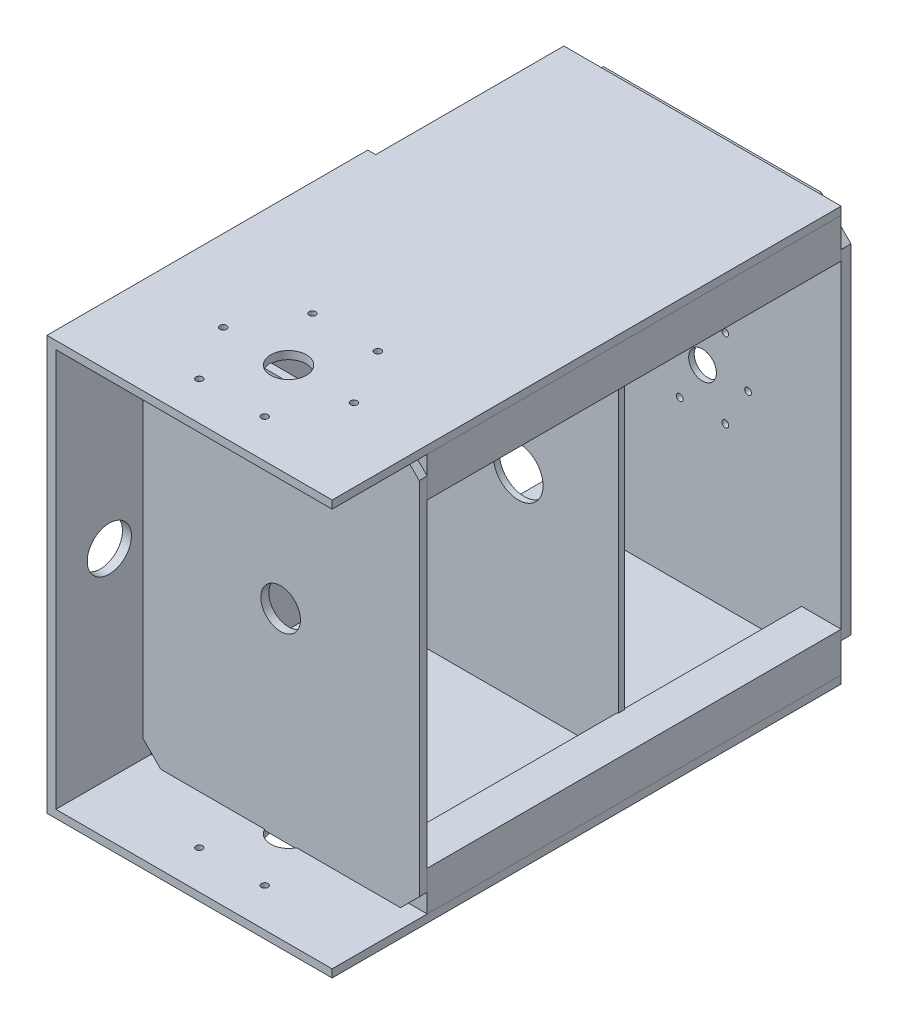
SolidWorks part; units mm, degrees
ref_plane "Front Plane" through (0, 0, 0) normal (0, 0, 1) x (1, 0, 0)
ref_plane "Top Plane" through (0, 0, 0) normal (0, 1, 0) x (1, 0, 0)
ref_plane "Right Plane" through (0, 0, 0) normal (1, 0, 0) x (0, 0, -1)
sketch "SK_Bottom_Plate" plane through (0, 0, 0) normal (0, 0, 1) x (1, 0, 0)
  line L0 (-55, -100.5) -> (55, -100.5)
  line L1 (55, -100.5) -> (70, -85.5)
  line L2 (70, -85.5) -> (70, 85.5)
  line L3 (70, 85.5) -> (55, 100.5)
  line L4 (55, 100.5) -> (-55, 100.5)
  line L5 (-55, 100.5) -> (-70, 85.5)
  line L6 (-70, 85.5) -> (-70, -85.5)
  line L7 (-70, -85.5) -> (-55, -100.5)
  circle A0 centre (23, 0) radius 1.7
  circle A1 centre (11.5, 19.9186) radius 1.7
  circle A2 centre (-11.5, 19.9186) radius 1.7
  circle A3 centre (-23, 0) radius 1.7
  circle A4 centre (-11.5, -19.9186) radius 1.7
  circle A5 centre (11.5, -19.9186) radius 1.7
  circle A6 centre (0, 0) radius 7
  circle A7 centre (60, 90.5) radius 2.75
  circle A8 centre (60, -90.5) radius 2.75
  circle A9 centre (-60, 90.5) radius 2.75
  circle A10 centre (-60, -90.5) radius 2.75
  dimension "D17_SK_Bottom_Plate" = 3.4
  dimension "D19_SK_Bottom_Plate" = 3.4
  dimension "D22_SK_Bottom_Plate" = 3.4
  dimension "D25_SK_Bottom_Plate" = 3.4
  dimension "D27_SK_Bottom_Plate" = 3.4
  dimension "D30_SK_Bottom_Plate" = 3.4
  dimension "D33_SK_Bottom_Plate" = 14
  dimension "D34_SK_Bottom_Plate" = 5.5
  dimension "D37_SK_Bottom_Plate" = 5.5
  dimension "D40_SK_Bottom_Plate" = 5.5
  dimension "D43_SK_Bottom_Plate" = 5.5
  dimension "P1" = 55
  dimension "P2" = 100.5
  dimension "P3" = 55
  dimension "P4" = 100.5
  dimension "P5" = 70
  dimension "P6" = 85.5
  dimension "P7" = 70
  dimension "P8" = 85.5
  dimension "P9" = 55
  dimension "P10" = 100.5
  dimension "P11" = 55
  dimension "P12" = 100.5
  dimension "P13" = 70
  dimension "P14" = 85.5
  dimension "P15" = 70
  dimension "P16" = 85.5
  dimension "P18" = 23
  dimension "P20" = 11.5
  dimension "P21" = 19.9186
  dimension "P23" = 11.5
  dimension "P24" = 19.9186
  dimension "P26" = 23
  dimension "P28" = 11.5
  dimension "P29" = 19.9186
  dimension "P31" = 11.5
  dimension "P32" = 19.9186
  dimension "P35" = 60
  dimension "P36" = 90.5
  dimension "P38" = 60
  dimension "P39" = 90.5
  dimension "P41" = 60
  dimension "P42" = 90.5
  dimension "P44" = 60
  dimension "P45" = 90.5
extrude "Bottom_Plate" add sketch "SK_Bottom_Plate" along normal blind 5
sketch "SK_Waist_Pilot_Recess" plane through (0, 0, 0) normal (0, 0, 1) x (1, 0, 0)
  circle A0 centre (0, 0) radius 17.15
  dimension "D1_SK_Waist_Pilot_Recess" = 34.3
extrude "Waist_Pilot_Recess" cut sketch "SK_Waist_Pilot_Recess" along normal blind 2.2
ref_plane "PL_Side_Left_base" through (0, 100.5, 0) normal (0, 1, 0) x (1, 0, 0)
sketch "SK_Side_Left" plane through (0, 100.5, 0) normal (0, 1, 0) x (1, 0, 0)
  line L0 (-70, -5) -> (70, -5)
  line L1 (70, -5) -> (70, -262)
  line L2 (70, -262) -> (-70, -262)
  line L3 (-70, -262) -> (-70, -5)
  circle A0 centre (33, -214) radius 1.7
  circle A1 centre (16.5, -185.4212) radius 1.7
  circle A2 centre (-16.5, -185.4212) radius 1.7
  circle A3 centre (-33, -214) radius 1.7
  circle A4 centre (-16.5, -242.5788) radius 1.7
  circle A5 centre (16.5, -242.5788) radius 1.7
  circle A6 centre (0, -214) radius 9
  dimension "D9_SK_Side_Left" = 3.4
  dimension "D12_SK_Side_Left" = 3.4
  dimension "D15_SK_Side_Left" = 3.4
  dimension "D18_SK_Side_Left" = 3.4
  dimension "D21_SK_Side_Left" = 3.4
  dimension "D24_SK_Side_Left" = 3.4
  dimension "D27_SK_Side_Left" = 18
  dimension "P1" = 70
  dimension "P2" = 5
  dimension "P3" = 70
  dimension "P4" = 5
  dimension "P5" = 70
  dimension "P6" = 262
  dimension "P7" = 70
  dimension "P8" = 262
  dimension "P10" = 33
  dimension "P11" = 214
  dimension "P13" = 16.5
  dimension "P14" = 185.4212
  dimension "P16" = 16.5
  dimension "P17" = 185.4212
  dimension "P19" = 33
  dimension "P20" = 214
  dimension "P22" = 16.5
  dimension "P23" = 242.5788
  dimension "P25" = 16.5
  dimension "P26" = 242.5788
  dimension "P28" = 214
extrude "Side_Left" add sketch "SK_Side_Left" along normal blind 4
ref_plane "PL_Side_Right_base" through (0, -104.5, 0) normal (0, 1, 0) x (1, 0, 0)
sketch "SK_Side_Right" plane through (0, -104.5, 0) normal (0, 1, 0) x (1, 0, 0)
  line L0 (-70, -5) -> (70, -5)
  line L1 (70, -5) -> (70, -262)
  line L2 (70, -262) -> (-70, -262)
  line L3 (-70, -262) -> (-70, -5)
  circle A0 centre (33, -214) radius 1.7
  circle A1 centre (16.5, -185.4212) radius 1.7
  circle A2 centre (-16.5, -185.4212) radius 1.7
  circle A3 centre (-33, -214) radius 1.7
  circle A4 centre (-16.5, -242.5788) radius 1.7
  circle A5 centre (16.5, -242.5788) radius 1.7
  circle A6 centre (0, -214) radius 9
  dimension "D9_SK_Side_Right" = 3.4
  dimension "D12_SK_Side_Right" = 3.4
  dimension "D15_SK_Side_Right" = 3.4
  dimension "D18_SK_Side_Right" = 3.4
  dimension "D21_SK_Side_Right" = 3.4
  dimension "D24_SK_Side_Right" = 3.4
  dimension "D27_SK_Side_Right" = 18
  dimension "P1" = 70
  dimension "P2" = 5
  dimension "P3" = 70
  dimension "P4" = 5
  dimension "P5" = 70
  dimension "P6" = 262
  dimension "P7" = 70
  dimension "P8" = 262
  dimension "P10" = 33
  dimension "P11" = 214
  dimension "P13" = 16.5
  dimension "P14" = 185.4212
  dimension "P16" = 16.5
  dimension "P17" = 185.4212
  dimension "P19" = 33
  dimension "P20" = 214
  dimension "P22" = 16.5
  dimension "P23" = 242.5788
  dimension "P25" = 16.5
  dimension "P26" = 242.5788
  dimension "P28" = 214
extrude "Side_Right" add sketch "SK_Side_Right" along normal blind 4
ref_plane "PL_Deck_base" through (0, 0, 214) normal (0, 0, 1) x (1, 0, 0)
sketch "SK_Deck" plane through (0, 0, 214) normal (0, 0, 1) x (1, 0, 0)
  line L0 (-60, -101) -> (60, -101)
  line L1 (60, -101) -> (70, -91)
  line L2 (70, -91) -> (70, 91)
  line L3 (70, 91) -> (60, 101)
  line L4 (60, 101) -> (-60, 101)
  line L5 (-60, 101) -> (-70, 91)
  line L6 (-70, 91) -> (-70, -91)
  line L7 (-70, -91) -> (-60, -101)
  circle A0 centre (0, 0) radius 10
  dimension "D17_SK_Deck" = 20
  dimension "P1" = 60
  dimension "P2" = 101
  dimension "P3" = 60
  dimension "P4" = 101
  dimension "P5" = 70
  dimension "P6" = 91
  dimension "P7" = 70
  dimension "P8" = 91
  dimension "P9" = 60
  dimension "P10" = 101
  dimension "P11" = 60
  dimension "P12" = 101
  dimension "P13" = 70
  dimension "P14" = 91
  dimension "P15" = 70
  dimension "P16" = 91
extrude "Deck" add sketch "SK_Deck" along normal blind 4
ref_plane "PL_Tray_base" through (0, 0, 95) normal (0, 0, 1) x (1, 0, 0)
sketch "SK_Tray" plane through (0, 0, 95) normal (0, 0, 1) x (1, 0, 0)
  line L0 (-50.5, -101) -> (50.5, -101)
  line L1 (50.5, -101) -> (50.5, 101)
  line L2 (50.5, 101) -> (-50.5, 101)
  line L3 (-50.5, 101) -> (-50.5, -101)
  circle A0 centre (0, 0) radius 12.5
  dimension "D9_SK_Tray" = 25
  dimension "P1" = 50.5
  dimension "P2" = 101
  dimension "P3" = 50.5
  dimension "P4" = 101
  dimension "P5" = 50.5
  dimension "P6" = 101
  dimension "P7" = 50.5
  dimension "P8" = 101
extrude "Tray" add sketch "SK_Tray" along normal blind 3
ref_plane "PL_Back_Plate_base" through (-74, 0, 0) normal (1, 0, 0) x (0, 0, -1)
sketch "SK_Back_Plate" plane through (-74, 0, 0) normal (1, 0, 0) x (0, 0, -1)
  line L0 (-100, -104.5) -> (-100, 104.5)
  line L1 (-100, 104.5) -> (-262, 104.5)
  line L2 (-262, 104.5) -> (-262, -104.5)
  line L3 (-262, -104.5) -> (-100, -104.5)
  circle A0 centre (-235, 0) radius 11.15
  dimension "D9_SK_Back_Plate" = 22.3
  dimension "P1" = 100
  dimension "P2" = 104.5
  dimension "P3" = 100
  dimension "P4" = 104.5
  dimension "P5" = 262
  dimension "P6" = 104.5
  dimension "P7" = 262
  dimension "P8" = 104.5
  dimension "P10" = 235
extrude "Back_Plate" add sketch "SK_Back_Plate" along normal blind 4.5
ref_plane "PL_Post_0_base" through (0, 0, 5) normal (0, 0, 1) x (1, 0, 0)
sketch "SK_Post_0" plane through (0, 0, 5) normal (0, 0, 1) x (1, 0, 0)
  line L0 (50, 80.5) -> (70, 80.5)
  line L1 (70, 80.5) -> (70, 100.5)
  line L2 (70, 100.5) -> (50, 100.5)
  line L3 (50, 100.5) -> (50, 80.5)
  dimension "P1" = 50
  dimension "P2" = 80.5
  dimension "P3" = 70
  dimension "P4" = 80.5
  dimension "P5" = 70
  dimension "P6" = 100.5
  dimension "P7" = 50
  dimension "P8" = 100.5
extrude "Post_0" add sketch "SK_Post_0" along normal blind 209 separate body
ref_plane "PL_Post_1_base" through (0, 0, 5) normal (0, 0, 1) x (1, 0, 0)
sketch "SK_Post_1" plane through (0, 0, 5) normal (0, 0, 1) x (1, 0, 0)
  line L0 (50, -100.5) -> (70, -100.5)
  line L1 (70, -100.5) -> (70, -80.5)
  line L2 (70, -80.5) -> (50, -80.5)
  line L3 (50, -80.5) -> (50, -100.5)
  dimension "P1" = 50
  dimension "P2" = 100.5
  dimension "P3" = 70
  dimension "P4" = 100.5
  dimension "P5" = 70
  dimension "P6" = 80.5
  dimension "P7" = 50
  dimension "P8" = 80.5
extrude "Post_1" add sketch "SK_Post_1" along normal blind 209 separate body
ref_plane "PL_Post_2_base" through (0, 0, 5) normal (0, 0, 1) x (1, 0, 0)
sketch "SK_Post_2" plane through (0, 0, 5) normal (0, 0, 1) x (1, 0, 0)
  line L0 (-70, 80.5) -> (-50, 80.5)
  line L1 (-50, 80.5) -> (-50, 100.5)
  line L2 (-50, 100.5) -> (-70, 100.5)
  line L3 (-70, 100.5) -> (-70, 80.5)
  dimension "P1" = 70
  dimension "P2" = 80.5
  dimension "P3" = 50
  dimension "P4" = 80.5
  dimension "P5" = 50
  dimension "P6" = 100.5
  dimension "P7" = 70
  dimension "P8" = 100.5
extrude "Post_2" add sketch "SK_Post_2" along normal blind 209 separate body
ref_plane "PL_Post_3_base" through (0, 0, 5) normal (0, 0, 1) x (1, 0, 0)
sketch "SK_Post_3" plane through (0, 0, 5) normal (0, 0, 1) x (1, 0, 0)
  line L0 (-70, -100.5) -> (-50, -100.5)
  line L1 (-50, -100.5) -> (-50, -80.5)
  line L2 (-50, -80.5) -> (-70, -80.5)
  line L3 (-70, -80.5) -> (-70, -100.5)
  dimension "P1" = 70
  dimension "P2" = 100.5
  dimension "P3" = 50
  dimension "P4" = 100.5
  dimension "P5" = 50
  dimension "P6" = 80.5
  dimension "P7" = 70
  dimension "P8" = 80.5
extrude "Post_3" add sketch "SK_Post_3" along normal blind 209 separate body
equation "\"Torso_half_depth\" = 70"
equation "\"Side_plate_y\" = 104.5"
equation "\"Shoulder_z\" = 214"
equation "\"Deck_z\" = 214"
